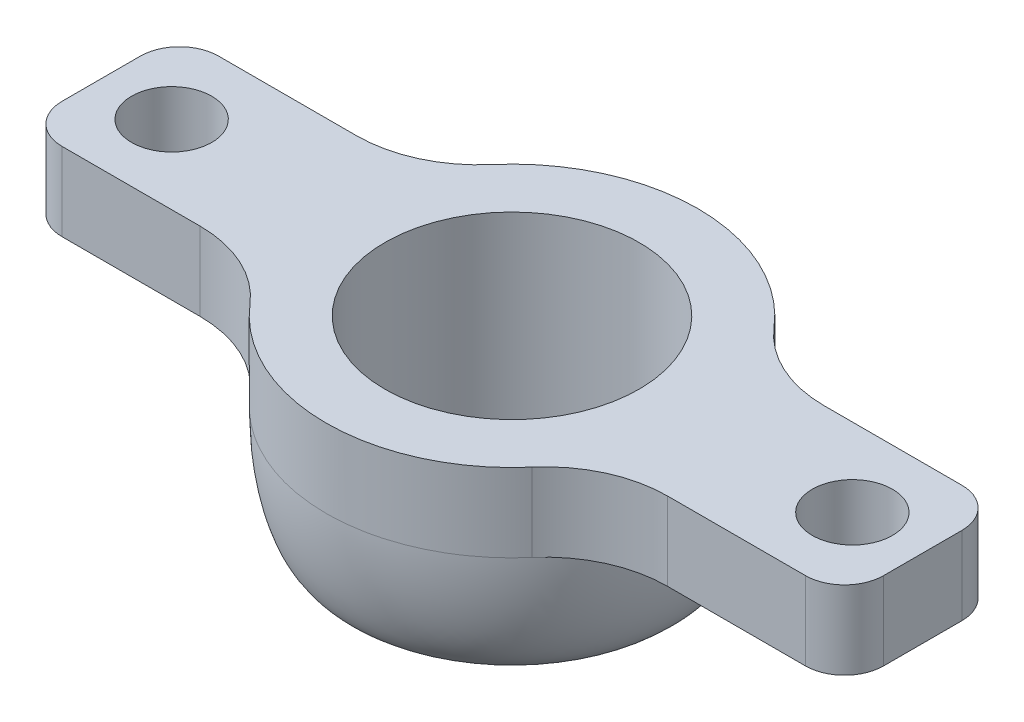
SolidWorks part; units mm, degrees
ref_plane "Front Plane" through (0, 0, 0) normal (0, 0, 1) x (1, 0, 0)
ref_plane "Top Plane" through (0, 0, 0) normal (0, 1, 0) x (1, 0, 0)
ref_plane "Right Plane" through (0, 0, 0) normal (1, 0, 0) x (0, 0, -1)
sketch "Sketch1" plane through (0, 0, 0) normal (0, 1, 0) x (1, 0, 0)
  circle A0 centre (0, 0) radius 3.25
  circle A1 centre (0, 0) radius 4.75
  dimension "D1" = 6.5
  dimension "D2" = 1.5
extrude "Boss-Extrude1" add sketch "Sketch1" along normal blind 5
sketch "Sketch2" plane through (0, 5, 0) normal (0, 1, 0) x (1, 0, 0)
  line L0 (-1.7118, -10.5508) -> (-5.4706, -9.1827)
  line L1 (-10.5, -2) -> (10.5, -2)
  line L2 (-10.5, -2) -> (-10.5, 2)
  line L3 (-10.5, 2) -> (10.5, 2)
  line L4 (10.5, -2) -> (10.5, 2)
  line L5 (-10.5, -2) -> (10.5, 2) construction
  line L6 (-10.5, 2) -> (10.5, -2) construction
  line L10 (-1.7118, -10.5508) -> (5.4706, 9.1827) [skipped]
  line L11 (5.4706, 9.1827) -> (1.7118, 10.5508) [skipped]
  line L12 (-5.4706, -9.1827) -> (1.7118, 10.5508) [skipped]
  point P0 (0, 0)
  point P13 (0, 0)
  circle M5 centre (0, 0) radius 4.75
  dimension "D1" = 21
  dimension "D3" = 4
  dimension "D2" = 2
extrude "Boss-Extrude2" add sketch "Sketch2" against normal blind 2 contours L1 L4 L3 M5 | L3 L2 L1 M5 region at (7.5514, 5, 0) region at (-7.5514, 5, 0)
sketch "Sketch3" plane through (0, 3, 0) normal (0, -1, 0) x (1, 0, 0)
  line L0 (0, 0) -> (10.5, 0)
  line L2 (10.5, 2) -> (10.5, -2) construction
  line L3 (10.5, 0) -> (0, 0)
  line L4 (0, 0) -> (8.7, 0)
  circle A2 centre (8.7, 0) radius 1.025
  circle A3 centre (-8.7, 0) radius 1.025
  point P11 (0.0022, 0)
  point P16 (0, 0)
  dimension "D2" = 2.05
  dimension "D1" = 8.7
  dimension "D3" = 2
extrude "Cut-Extrude1" cut sketch "Sketch3" against normal through all contours L3 A2 L4 | L4 A2 L3 | A3 region at (8.7, 3, 0.435) region at (8.7, 3, -0.435) region at (-8.7, 3, 0)
fillet "Fillet1" radius 3.125 4 edges at (4.3084, 4, 2) (-4.3084, 4, 2) (-4.3084, 4, -2) (4.3084, 4, -2)
fillet "Fillet2" radius 1 4 edges at (-10.5, 4, -2) (-10.5, 4, 2) (10.5, 4, 2) (10.5, 4, -2)
fillet "Fillet3" radius 1 1 edges at (0, 0, 4.75) second distance 3 first distance on face at (0, 0, 4.75)
ref_plane "Plane1" through (0, 0, -4.75) normal (0, 0, -1) x (-1, 0, 0)
ref_plane "Plane2" through (0, 0, 0) normal (0, -1, 0) x (-1, 0, 0)
ref_plane "Plane3" through (-10.5, 0, 0) normal (-1, 0, 0) x (0, 0, 1)
ref_axis "Axis2" through (3.9729, 0, -4.75) along (-1, 0, 0)
ref_point "Point1"
